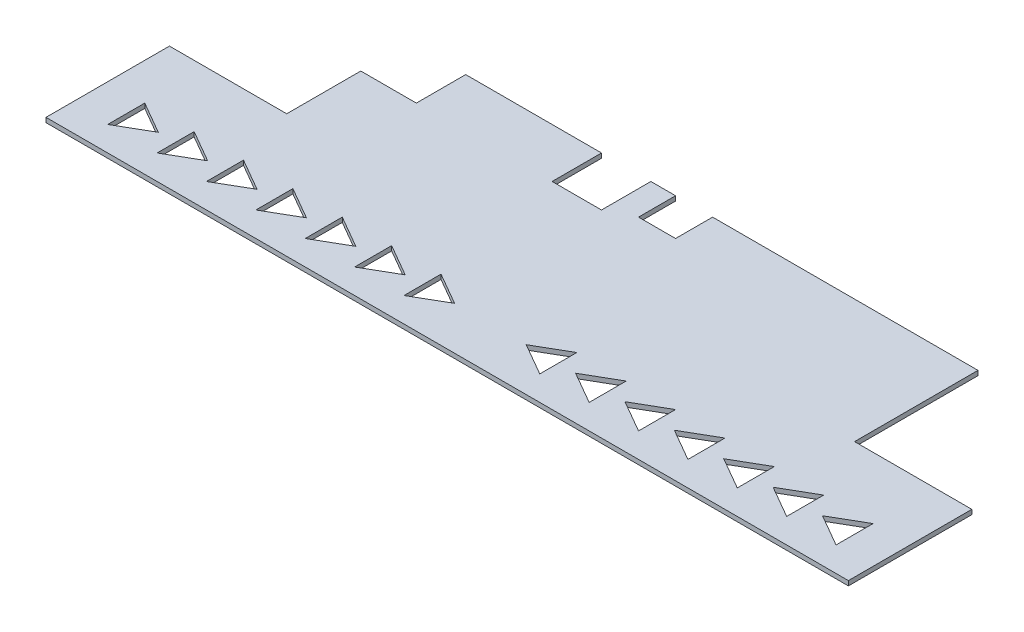
SolidWorks part; units mm, degrees
note: The reader was unsure of these and kept them because the rebuilt part matched: thickness of "Base-Flange1", "Sheet-Metal1", "Sheet-Metal2", "Sheet-Metal3", "Sheet-Metal4".
material "6061 Alloy"
ref_plane "Front Plane" through (0, 0, 0) normal (0, 0, 1) x (1, 0, 0)
ref_plane "Top Plane" through (0, 0, 0) normal (0, 1, 0) x (1, 0, 0)
ref_plane "Right Plane" through (0, 0, 0) normal (1, 0, 0) x (0, 0, -1)
sketch "Sketch1" plane through (0, 0, 0) normal (0, 1, 0) x (1, 0, 0)
  line L1 (412.75, 127) -> (-412.75, 127)
  line L2 (412.75, 127) -> (412.75, -127)
  line L3 (412.75, -127) -> (-412.75, -127)
  line L4 (-412.75, 127) -> (-412.75, -127)
  line L5 (412.75, 127) -> (-412.75, -127) construction
  line L6 (412.75, -127) -> (-412.75, 127) construction
  point P0 (0, 0)
  dimension "D1" = 254
  dimension "D2" = 825.5
base flange "Base-Flange1" sketch "Sketch1" thickness 4.7625 reverse thickness direction no parameters "D1"=3.175
sketch "Sketch6" plane through (0, 0, 0) normal (0, 1, 0) x (1, 0, 0)
  line L0 (412.75, 127) -> (-412.75, 127) construction
  line L1 (-19.05, 165.1) -> (19.05, 165.1)
  line L2 (-19.05, 165.1) -> (-19.05, 88.9)
  line L3 (-19.05, 88.9) -> (19.05, 88.9)
  line L4 (19.05, 165.1) -> (19.05, 88.9)
  line L5 (-19.05, 165.1) -> (19.05, 88.9) construction
  line L6 (-19.05, 88.9) -> (19.05, 165.1) construction
  line L7 (-412.75, 127) -> (-412.75, -127) construction
  line L8 (-533.4, 101.6) -> (-292.1, 101.6)
  line L9 (-533.4, 101.6) -> (-533.4, 0)
  line L10 (-533.4, 0) -> (-292.1, 0)
  line L11 (-292.1, 101.6) -> (-292.1, 0)
  line L12 (-533.4, 101.6) -> (-292.1, 0) construction
  line L13 (-533.4, 0) -> (-292.1, 101.6) construction
  line L14 (412.75, -127) -> (412.75, 127) construction
  line L15 (533.4, 0) -> (292.1, 0)
  line L16 (533.4, 0) -> (533.4, 101.6)
  line L17 (533.4, 101.6) -> (292.1, 101.6)
  line L18 (292.1, 0) -> (292.1, 101.6)
  line L19 (533.4, 0) -> (292.1, 101.6) construction
  line L20 (533.4, 101.6) -> (292.1, 0) construction
  line L22 (-44.45, 76.2) -> (-95.25, 76.2)
  line L23 (-44.45, 76.2) -> (-44.45, 177.8)
  line L24 (-44.45, 177.8) -> (-95.25, 177.8)
  line L25 (-95.25, 76.2) -> (-95.25, 177.8)
  line L26 (-44.45, 76.2) -> (-95.25, 177.8) construction
  line L27 (-44.45, 177.8) -> (-95.25, 76.2) construction
  point P0 (0, 127)
  point P7 (-412.75, 50.8)
  point P14 (412.75, 50.8)
  point P21 (-69.85, 127)
  dimension "D1" = 38.1
  dimension "D2" = 76.2
  dimension "D3" = 241.3
  dimension "D4" = 101.6
  dimension "D5" = 25.4
  dimension "D6" = 241.3
  dimension "D7" = 101.6
  dimension "D8" = 25.4
  dimension "D9" = 50.8
  dimension "D10" = 101.6
  dimension "D11" = 25.4
extrude "Cut-Extrude1" cut sketch "Sketch6" against normal through all normal cut yes
sketch "Sketch7" plane through (0, 0, 0) normal (0, 1, 0) x (1, 0, 0)
  line L1 (-412.75, 127) -> (-234.95, 127)
  line L2 (-412.75, 127) -> (-412.75, 76.2)
  line L3 (-412.75, 76.2) -> (-234.95, 76.2)
  line L4 (-234.95, 127) -> (-234.95, 76.2)
  line L5 (412.75, 127) -> (292.1, 127)
  line L6 (412.75, 127) -> (412.75, 101.6)
  line L7 (412.75, 101.6) -> (292.1, 101.6)
  line L8 (292.1, 127) -> (292.1, 101.6)
  dimension "D1" = 50.8
  dimension "D2" = 177.8
extrude "Cut-Extrude2" cut sketch "Sketch7" against normal through all normal cut yes
sketch "Sketch8" plane through (0, 0, 0) normal (0, 1, 0) x (1, 0, 0)
  line L0 (412.75, -127) -> (412.75, 0) construction
  line L1 (341.6544, -82.55) -> (374.65, -101.6)
  line L2 (374.65, -101.6) -> (374.65, -63.5)
  line L3 (374.65, -63.5) -> (341.6544, -82.55)
  line L4 (323.85, -101.6) -> (323.85, -63.5)
  line L5 (323.85, -63.5) -> (290.8544, -82.55)
  line L6 (290.8544, -82.55) -> (323.85, -101.6)
  line L7 (273.05, -101.6) -> (273.05, -63.5)
  line L8 (273.05, -63.5) -> (240.0544, -82.55)
  line L9 (240.0544, -82.55) -> (273.05, -101.6)
  line L10 (222.25, -101.6) -> (222.25, -63.5)
  line L11 (222.25, -63.5) -> (189.2544, -82.55)
  line L12 (189.2544, -82.55) -> (222.25, -101.6)
  line L13 (171.45, -101.6) -> (171.45, -63.5)
  line L14 (171.45, -63.5) -> (138.4544, -82.55)
  line L15 (138.4544, -82.55) -> (171.45, -101.6)
  line L16 (120.65, -101.6) -> (120.65, -63.5)
  line L17 (120.65, -63.5) -> (87.6544, -82.55)
  line L18 (87.6544, -82.55) -> (120.65, -101.6)
  line L19 (69.85, -101.6) -> (69.85, -63.5)
  line L20 (69.85, -63.5) -> (36.8544, -82.55)
  line L21 (36.8544, -82.55) -> (69.85, -101.6)
  line L22 (0, 0) -> (0, -95.9685) construction
  line L23 (-36.8544, -82.55) -> (-69.85, -101.6)
  line L24 (-69.85, -63.5) -> (-36.8544, -82.55)
  line L25 (-69.85, -101.6) -> (-69.85, -63.5)
  line L26 (-87.6544, -82.55) -> (-120.65, -101.6)
  line L27 (-120.65, -63.5) -> (-87.6544, -82.55)
  line L28 (-120.65, -101.6) -> (-120.65, -63.5)
  line L29 (-138.4544, -82.55) -> (-171.45, -101.6)
  line L30 (-171.45, -63.5) -> (-138.4544, -82.55)
  line L31 (-171.45, -101.6) -> (-171.45, -63.5)
  line L32 (-189.2544, -82.55) -> (-222.25, -101.6)
  line L33 (-222.25, -63.5) -> (-189.2544, -82.55)
  line L34 (-222.25, -101.6) -> (-222.25, -63.5)
  line L35 (-240.0544, -82.55) -> (-273.05, -101.6)
  line L36 (-273.05, -63.5) -> (-240.0544, -82.55)
  line L37 (-273.05, -101.6) -> (-273.05, -63.5)
  line L38 (-290.8544, -82.55) -> (-323.85, -101.6)
  line L39 (-323.85, -63.5) -> (-290.8544, -82.55)
  line L40 (-323.85, -101.6) -> (-323.85, -63.5)
  line L41 (-374.65, -63.5) -> (-341.6544, -82.55)
  line L42 (-374.65, -101.6) -> (-374.65, -63.5)
  line L43 (-341.6544, -82.55) -> (-374.65, -101.6)
  line L46 (-412.75, -127) -> (412.75, -127) construction
  line L47 (19.05, -101.6) -> (19.05, -63.5) [skipped]
  line L48 (-13.9456, -82.55) -> (19.05, -101.6) [skipped]
  line L49 (19.05, -63.5) -> (-13.9456, -82.55) [skipped]
  line L50 (-31.75, -63.5) -> (-64.7456, -82.55) [skipped]
  line L51 (-31.75, -101.6) -> (-31.75, -63.5) [skipped]
  line L52 (-64.7456, -82.55) -> (-31.75, -101.6) [skipped]
  line L53 (-82.55, -101.6) -> (-82.55, -63.5) [skipped]
  line L54 (-82.55, -63.5) -> (-115.5456, -82.55) [skipped]
  line L55 (-115.5456, -82.55) -> (-82.55, -101.6) [skipped]
  line L56 (-133.35, -101.6) -> (-133.35, -63.5) [skipped]
  line L57 (-133.35, -63.5) -> (-166.3456, -82.55) [skipped]
  line L58 (-166.3456, -82.55) -> (-133.35, -101.6) [skipped]
  line L59 (-184.15, -101.6) -> (-184.15, -63.5) [skipped]
  line L60 (-184.15, -63.5) -> (-217.1456, -82.55) [skipped]
  line L61 (-217.1456, -82.55) -> (-184.15, -101.6) [skipped]
  line L62 (-234.95, -101.6) -> (-234.95, -63.5) [skipped]
  line L63 (-234.95, -63.5) -> (-267.9456, -82.55) [skipped]
  line L64 (-267.9456, -82.55) -> (-234.95, -101.6) [skipped]
  line L65 (-285.75, -101.6) -> (-285.75, -63.5) [skipped]
  line L66 (-285.75, -63.5) -> (-318.7456, -82.55) [skipped]
  line L67 (-318.7456, -82.55) -> (-285.75, -101.6) [skipped]
  line L68 (-336.55, -101.6) -> (-336.55, -63.5) [skipped]
  line L69 (-336.55, -63.5) -> (-369.5456, -82.55) [skipped]
  line L70 (-369.5456, -82.55) -> (-336.55, -101.6) [skipped]
  circle A0 centre (363.6515, -82.55) radius 10.9985 construction
  circle A1 centre (-363.6515, -82.55) radius 10.9985 construction
  dimension "D1" = 38.1
  dimension "D2" = 38.1
  dimension "D4" = 25.4
  dimension "D3" = 15
extrude "Cut-Extrude3" cut sketch "Sketch8" against normal through all normal cut yes
sketch "Bend-Lines1" [suppressed] plane through (0, 0, 0) normal (0, 1, 0) x (1, 0, 0)
sketch "Bounding-Box1" [suppressed] plane through (0, 0, 0) normal (0, 1, 0) x (1, 0, 0)
sheet metal parameters "Sheet-Metal1" thickness 4.7625 parameters "D1"=3.175, "D7"=6.35
flat pattern "Flat-Pattern1" [suppressed]
sketch "Bend-Lines2" plane through (0, 0, 0) normal (0, 1, 0) x (1, 0, 0)
sketch "Bounding-Box2" [suppressed] plane through (0, 0, 0) normal (0, 1, 0) x (1, 0, 0)
sheet metal parameters "Sheet-Metal2" thickness 4.7625 parameters "D1"=3.175, "D7"=6.35
flat pattern "Flat-Pattern1"
sketch "Bend-Lines2" plane through (0, 0, 0) normal (0, 1, 0) x (1, 0, 0)
sketch "Bounding-Box2" [suppressed] plane through (0, 0, 0) normal (0, 1, 0) x (1, 0, 0)
sheet metal parameters "Sheet-Metal3" thickness 4.7625 parameters "D1"=3.175, "D7"=6.35
flat pattern "Flat-Pattern1"
sketch "Bend-Lines2" plane through (0, 0, 0) normal (0, 1, 0) x (1, 0, 0)
sketch "Bounding-Box2" [suppressed] plane through (0, 0, 0) normal (0, 1, 0) x (1, 0, 0)
sheet metal parameters "Sheet-Metal4" thickness 4.7625 parameters "D1"=3.175, "D7"=6.35
flat pattern "Flat-Pattern1"
sketch "Bend-Lines2" plane through (0, 0, 0) normal (0, 1, 0) x (1, 0, 0)
sketch3d "Bounding-Box2" [suppressed]
  line L0 (412.75, 127, 0) -> (-412.75, 127, 0) construction
  line L1 (412.75, -127, 0) -> (-412.75, -127, 0) construction
  line L2 (412.75, 127, 0) -> (412.75, -127, 0) construction
  line L3 (-412.75, 127, 0) -> (-412.75, -127, 0) construction
